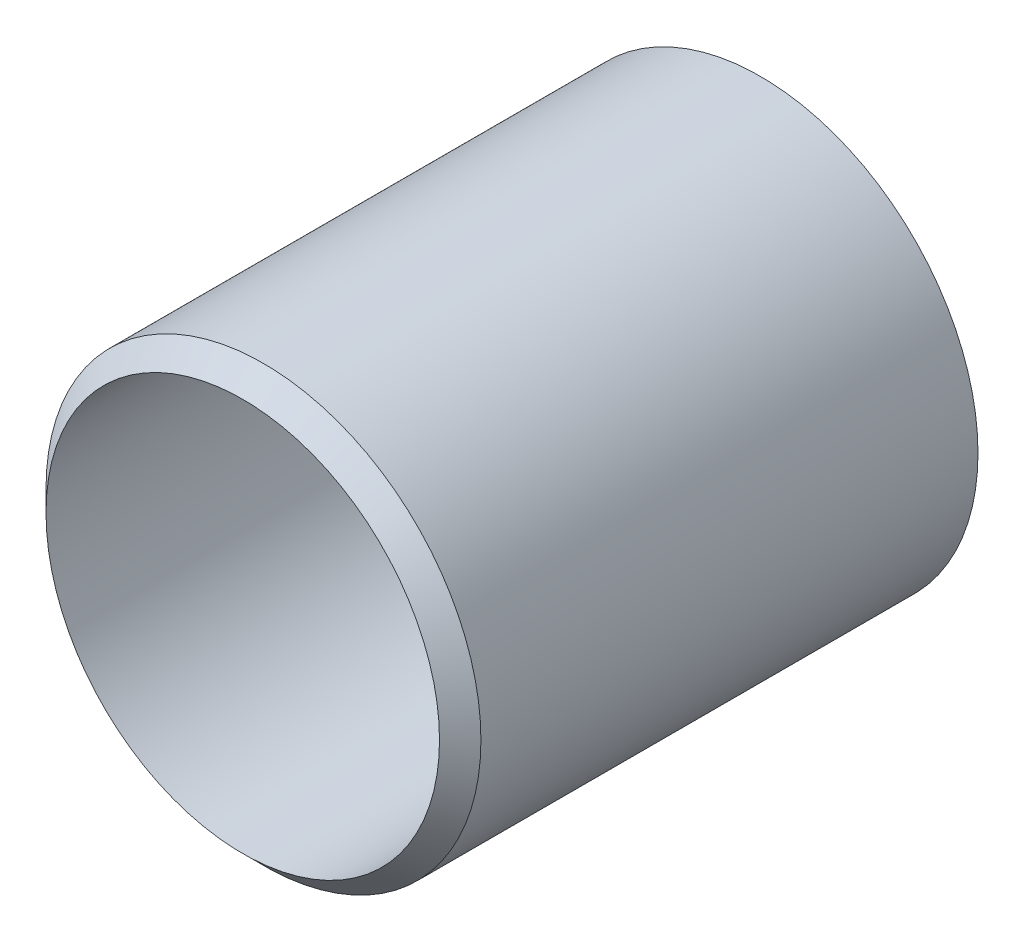
SolidWorks part; units mm, degrees
material "ABS"
ref_plane "Plan de face" through (0, 0, 0) normal (0, 0, 1) x (1, 0, 0)
ref_plane "Plan de dessus" through (0, 0, 0) normal (0, 1, 0) x (1, 0, 0)
ref_plane "Plan de droite" through (0, 0, 0) normal (1, 0, 0) x (0, 0, -1)
sketch "Esquisse1" plane through (0, 0, 0) normal (0, 0, 1) x (1, 0, 0)
  circle A0 centre (0, 0) radius 28.5
  circle A1 centre (0, 0) radius 31.5
  dimension "D1" = 57
  dimension "D2" = 63
extrude "Boss.-Extru.1" add sketch "Esquisse1" along normal blind 76
chamfer "Chanfrein1" distance 4 angle 45 1 edges at (31.5, 0, 76)
